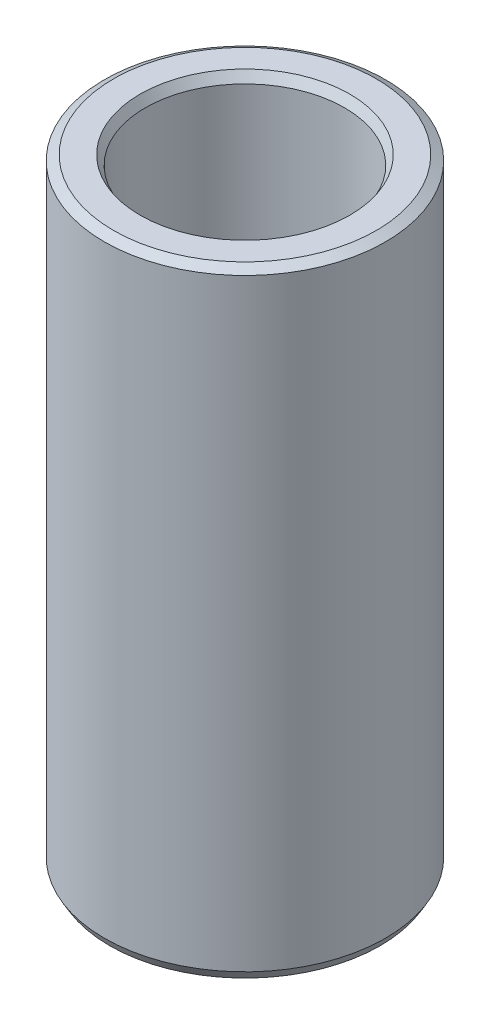
SolidWorks part; units mm, degrees
ref_plane "Front Plane" through (0, 0, 0) normal (0, 0, 1) x (1, 0, 0)
ref_plane "Top Plane" through (0, 0, 0) normal (0, 1, 0) x (1, 0, 0)
ref_plane "Right Plane" through (0, 0, 0) normal (1, 0, 0) x (0, 0, -1)
sketch "Sketch1" plane through (0, 0, 0) normal (0, 1, 0) x (1, 0, 0)
  circle A0 centre (0, 0) radius 30
  dimension "SLEEVE_OD" = 60
extrude "Boss-Extrude1" add sketch "Sketch1" along normal blind 131.8002
sketch "Sketch2" plane through (0, 0, 0) normal (0, 1, 0) x (1, 0, 0)
  circle A0 centre (0, 0) radius 21.2611
  dimension "BORE_D" = 42.5222
extrude "Cut-Extrude1" cut sketch "Sketch2" along normal through all
chamfer "Chamfer1" distance 1.1292 angle 60 4 edges at (0, 131.8002, 21.2611) (0, 0, 21.2611) (0, 0, 30) (0, 131.8002, 30) first distance on face at (0, 131.8002, 21.2611) first distance on face at (0, 0, 21.2611) first distance on face at (0, 131.8002, 30)
